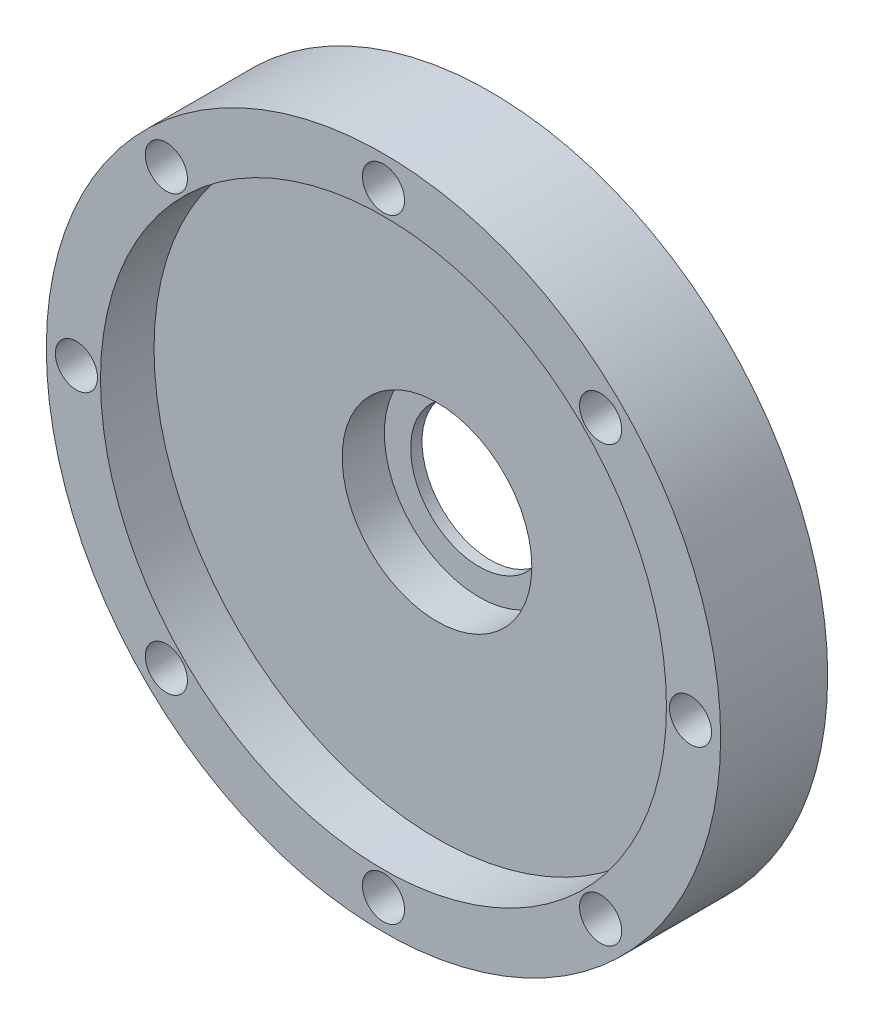
SolidWorks part; units mm, degrees
material "ABS"
ref_plane "Front Plane" through (0, 0, 0) normal (0, 0, 1) x (1, 0, 0)
ref_plane "Top Plane" through (0, 0, 0) normal (0, 1, 0) x (1, 0, 0)
ref_plane "Right Plane" through (0, 0, 0) normal (1, 0, 0) x (0, 0, -1)
sketch "Sketch1" plane through (0, 0, 0) normal (0, 0, 1) x (1, 0, 0)
  circle A0 centre (0, 0) radius 32.004
  dimension "D1" = 64.008
extrude "Boss-Extrude1" add sketch "Sketch1" along normal blind 10.16
sketch "Sketch2" plane through (0, 0, 10.16) normal (0, 0, 1) x (1, 0, 0)
  circle A0 centre (0, 0) radius 26.8605
  dimension "D1" = 53.721
extrude "Cut-Extrude1" cut sketch "Sketch2" against normal blind 5.08
sketch "Sketch3" plane through (0, 0, 5.08) normal (0, 0, 1) x (1, 0, 0)
  circle A0 centre (0, 0) radius 9
  dimension "D1" = 18
extrude "Cut-Extrude2" cut sketch "Sketch3" against normal blind 4
sketch "Sketch4" plane through (0, 0, 1.08) normal (0, 0, 1) x (1, 0, 0)
  circle A0 centre (0, 0) radius 6.5
  dimension "D1" = 13
extrude "Cut-Extrude3" cut sketch "Sketch4" against normal through all
sketch "Sketch5" plane through (0, 0, 10.16) normal (0, 0, 1) x (1, 0, 0)
  line L0 (0, 0) -> (0, 32.004) construction
  line L2 (0, 0) -> (22.6302, 22.6302) construction
  line L3 (0, 0) -> (32.004, 0) construction
  line L4 (0, 0) -> (22.6302, -22.6302) construction
  line L5 (0, 0) -> (0, -32.004) construction
  line L6 (0, 0) -> (-22.6302, -22.6302) construction
  line L7 (0, 0) -> (-32.004, 0) construction
  line L8 (0, 0) -> (-22.6302, 22.6302) construction
  line L9 (0, 0) -> (0, 29.1465) construction
  circle A0 centre (0, 0) radius 32.004 construction
  circle A1 centre (0, 29.1465) radius 2
  circle A2 centre (20.6097, 20.6097) radius 2
  circle A3 centre (29.1465, 0) radius 2
  circle A4 centre (20.6097, -20.6097) radius 2
  circle A5 centre (0, -29.1465) radius 2
  circle A6 centre (-20.6097, -20.6097) radius 2
  circle A7 centre (-29.1465, 0) radius 2
  circle A8 centre (-20.6097, 20.6097) radius 2
  point P6 (0, 29.1465)
  point P15 (20.6097, 20.6097)
  point P17 (29.1465, 0)
  point P19 (20.6097, -20.6097)
  point P21 (0, -29.1465)
  point P23 (-20.6097, -20.6097)
  point P25 (-29.1465, 0)
  point P27 (-20.6097, 20.6097)
  point P51 (0, 0)
  point P52 (0, 0)
  point P53 (20.6097, 20.6097)
  dimension "D3" = 4
  dimension "D1" = 29.1465
  dimension "D2" = 8
  dimension "D4" = 8
extrude "Cut-Extrude4" cut sketch "Sketch5" against normal through all
